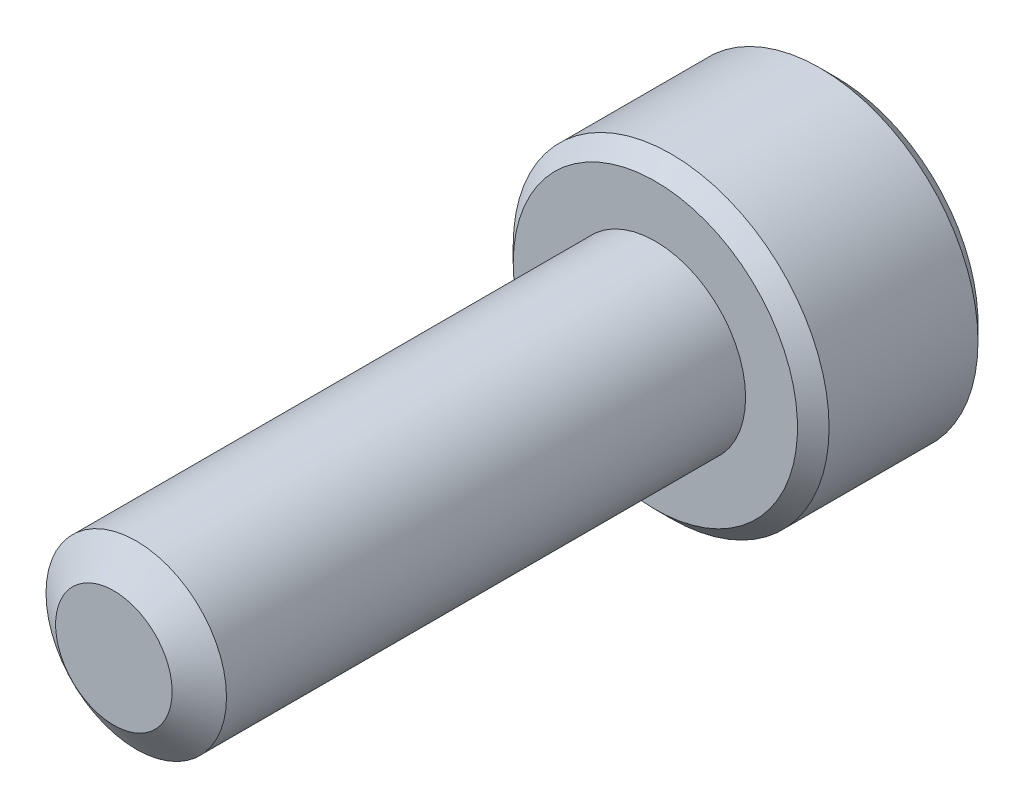
SolidWorks part; units mm, degrees
other "DetailItem1"
ref_plane "Front Plane" through (0, 0, 0) normal (0, 0, 1) x (1, 0, 0)
ref_plane "Top Plane" through (0, 0, 0) normal (0, 1, 0) x (1, 0, 0)
ref_plane "Right Plane" through (0, 0, 0) normal (1, 0, 0) x (0, 0, -1)
sketch "Sketch1" plane through (0, 0, 0) normal (0, 0, 1) x (1, 0, 0)
  circle A0 centre (0, 0) radius 2
  dimension "OD" = 4
extrude "Extrude1" add sketch "Sketch1" against normal blind 12
sketch "Sketch2" plane through (0, 0, 0) normal (0, 0, 1) x (1, 0, 0)
  circle A0 centre (0, 0) radius 2 construction
  circle A1 centre (0, 0) radius 2
curve "Helix/Spiral1" pitch 0.7 height 12.7 turns 18.1429 parameters "pitch"=0.7
sketch "Sketch3" plane through (0, 0, 0) normal (1, 0, 0) x (0, 0, -1)
  line L0 (-0.6125, 2) -> (-0.35, 1.5453)
  line L1 (-0.35, 1.5453) -> (-0.2625, 1.5453)
  line L2 (-0.2625, 1.5453) -> (0, 2)
  line L3 (-0.6125, 2) -> (0, 2)
  line L4 (-0.3062, 2) -> (-0.3062, 1.5453) construction
  line L5 (-0.4812, 1.7727) -> (-0.1312, 1.7727) construction
  line L6 (0, 2) -> (0, -2) construction
  dimension "D1" = 0.0875
  dimension "D2" = 0.35
  dimension "D3" = 60
sweep "Cut-Sweep1" [suppressed] cut profiles "Sketch3" path "Helix/Spiral1"
sketch "Sketch4" plane through (0, 0, 0) normal (1, 0, 0) x (0, 0, -1)
  line L0 (0.4962, 2) -> (0, 1.2913)
  line L1 (0, 1.2913) -> (0, 2)
  line L2 (0.4962, 2) -> (0, 2)
  line L3 (-0.6125, 2) -> (0, 2) construction
  line L4 (0, 0) -> (7.0209, 0) construction
  dimension "D1" = 55
  dimension "D2" = 0.254
revolve "Cut-Revolve1" cut sketch "Sketch4" angle 360 about L4
sketch "Sketch6" plane through (0, 0, -12) normal (0, 0, -1) x (-1, 0, 0)
  circle A0 centre (0, 0) radius 3.5
  dimension "head dia" = 7
extrude "Extrude2" add sketch "Sketch6" along normal blind 4
sketch "Sketch7" plane through (0, 0, -16) normal (0, 0, -1) x (-1, 0, 0)
  line L1 (0, 1.7321) -> (-1.5, 0.866)
  line L2 (-1.5, 0.866) -> (-1.5, -0.866)
  line L3 (-1.5, -0.866) -> (0, -1.7321)
  line L4 (0, -1.7321) -> (1.5, -0.866)
  line L5 (1.5, -0.866) -> (1.5, 0.866)
  line L6 (1.5, 0.866) -> (0, 1.7321)
  circle A0 centre (0, 0) radius 1.5 construction
  dimension "hex dia" = 3
extrude "Cut-Extrude1" cut sketch "Sketch7" against normal blind 2.25
sketch "Sketch8" plane through (0, 0, -16) normal (0, 0, -1) x (-1, 0, 0)
  circle A0 centre (0, 0) radius 1.7321
extrude "Cut-Extrude2" cut sketch "Sketch8" against normal through all draft 45
chamfer "Chamfer1" distance 0.35 angle 45 2 edges at (-3.5, 0, -16) (-3.5, 0, -12)
sketch "Sketch10" plane through (0, 0, -12) normal (0, 0, 1) x (1, 0, 0)
  circle A1 centre (0, 0) radius 2
  circle A2 centre (0, 0) radius 2
  dimension "D1" = 0
ref_plane "Plane1" through (0, 0, 0) normal (0, 0, 1) x (1, 0, 0)
extrude "partial thread" [suppressed] add sketch "Sketch10" along normal up to surface (10 mm away) separate body up to plane "Plane1"
chamfer "Chamfer2" [suppressed] distance 0.08 angle 45
combine bodies "Combine1" [suppressed] operation type add bodies to combine 107 108
sketch "Sketch9" plane through (0, 0, 0) normal (1, 0, 0) x (0, 0, -1)
  line L0 (0, 2) -> (0, -2) construction
  line L1 (1.75, 2) -> (1.75, -2) construction
  dimension "D1" = 1.75
equation "\"D3@Helix/Spiral1\" = \"screw length@Extrude1\"+\"pitch@Helix/Spiral1\""
equation "\"D1@Sketch3\" = \"pitch@Helix/Spiral1\"*.125"
equation "\"D2@Sketch3\" = \"pitch@Helix/Spiral1\"*.5"
equation "\"D1@Cut-Extrude1\" = \"hex dia@Sketch7\"*.75"
equation "\"D1@Chamfer1\" = \"head dia@Sketch6\"*.05"
equation "\"D1@Sketch9\" = \"pitch@Helix/Spiral1\"*2.5"
equation "\"D1@Chamfer2\"=\"OD@Sketch1\"*.02"
